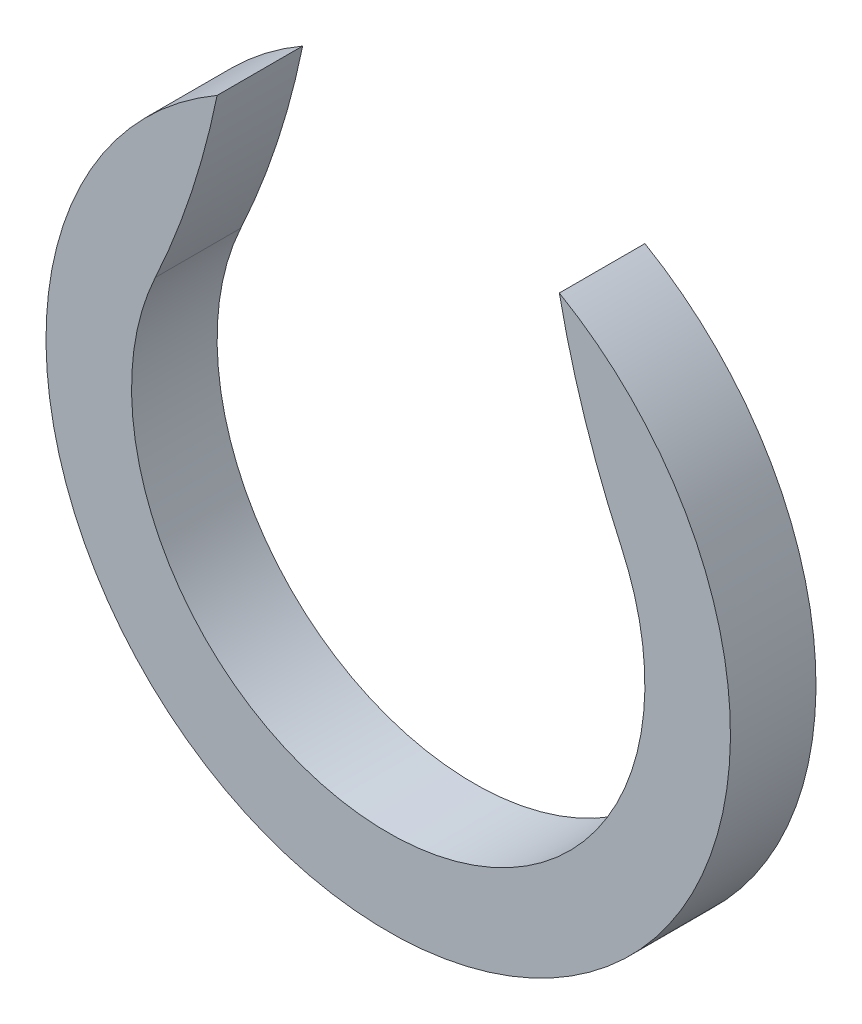
SolidWorks part; units mm, degrees
ref_plane "Front Plane" through (0, 0, 0) normal (0, 0, 1) x (1, 0, 0)
ref_plane "Top Plane" through (0, 0, 0) normal (0, 1, 0) x (1, 0, 0)
ref_plane "Right Plane" through (0, 0, 0) normal (1, 0, 0) x (0, 0, -1)
sketch "Esboço1" plane through (0, 0, 0) normal (0, 0, 1) x (1, 0, 0)
  line L0 (0, 0) -> (-2, 0) construction
  line L1 (-2, 2.2361) -> (-2, 3.4641)
  line L2 (-2, 0) -> (10.7027, 0) construction
  line L3 (2, 2.2361) -> (2, 3.4641)
  arc A0 (-2, 2.2361) -> (2, 2.2361) centre (0, 0) ccw
  arc A1 (-2, 3.4641) -> (2, 3.4641) centre (0, 0) ccw
  dimension "D1" = 6
  dimension "D2" = 1
  dimension "D3" = 2
extrude "Ressalto-extrusão1" add sketch "Esboço1" along normal blind 1
fillet "Filete1" radius 10 2 edges at (2, 2.2361, 0.5) (-2, 2.2361, 0.5)
